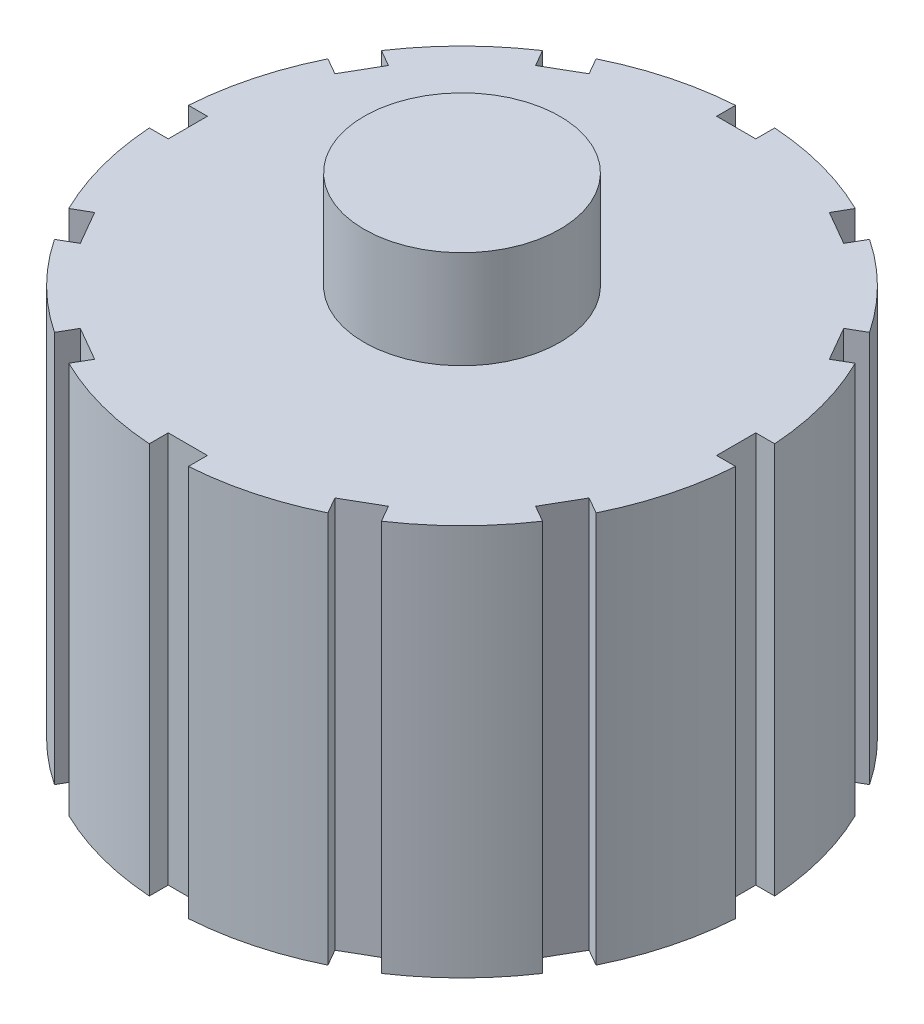
SolidWorks part; units mm, degrees
ref_plane "前视基准面" through (0, 0, 0) normal (0, 0, 1) x (1, 0, 0)
ref_plane "上视基准面" through (0, 0, 0) normal (0, 1, 0) x (1, 0, 0)
ref_plane "右视基准面" through (0, 0, 0) normal (1, 0, 0) x (0, 0, -1)
sketch "草图1" plane through (0, 0, 0) normal (0, 1, 0) x (1, 0, 0)
  circle A0 centre (0, 0) radius 15
extrude "凸台-拉伸1" add sketch "草图1" along normal blind 20
ref_plane "基准面1" through (0, 20, 0) normal (0, 1, 0) x (1, 0, 0)
sketch "草图2" plane through (0, 20, 0) normal (0, 1, 0) x (1, 0, 0)
  circle A0 centre (0, 0) radius 5
extrude "凸台-拉伸2" add sketch "草图2" along normal blind 5
sketch "草图3" plane through (0, 0, 0) normal (0, 1, 0) x (1, 0, 0)
  line L0 (14, 1) -> (16, 1)
  line L1 (16, 1) -> (16, -1)
  line L2 (16, -1) -> (14, -1)
  line L3 (14, -1) -> (14, 1)
extrude "切除-拉伸1" cut sketch "草图3" along normal through all
ref_axis "基准轴1" through (0, -1.25, 0) along (0, 1, 0)
pattern_circular "阵列(圆周)1" count 12 over 360 about axis through (0, -1.25, 0) along (0, 1, 0) of "切除-拉伸1"
sketch "草图4" plane through (0, 0, 0) normal (0, 1, 0) x (1, 0, 0)
  circle A0 centre (0, 0) radius 3
extrude "切除-拉伸2" cut sketch "草图4" along normal blind 12
